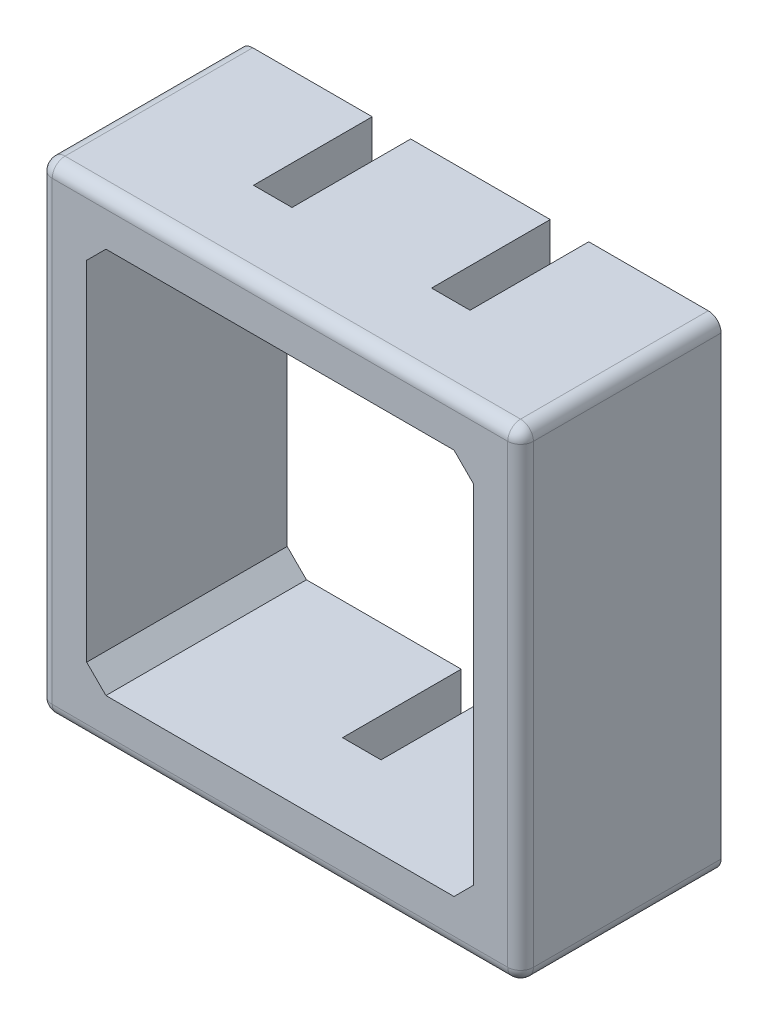
SolidWorks part; units mm, degrees
material "Nylon 101"
ref_plane "Front Plane" through (0, 0, 0) normal (0, 0, 1) x (1, 0, 0)
ref_plane "Top Plane" through (0, 0, 0) normal (0, 1, 0) x (1, 0, 0)
ref_plane "Right Plane" through (0, 0, 0) normal (1, 0, 0) x (0, 0, -1)
sketch "Sketch1" plane through (0, 0, 0) normal (0, 0, 1) x (1, 0, 0)
  line L0 (5.0482, -114.0142) -> (20.3517, -114.0142)
  line L1 (20.3517, -114.0142) -> (20.3517, -98.7107)
  line L2 (20.3517, -98.7107) -> (5.0482, -98.7107)
  line L3 (5.0482, -98.7107) -> (5.0482, -114.0142)
  line L4 (3.175, -115.8875) -> (22.225, -115.8875)
  line L5 (22.225, -115.8875) -> (22.225, -96.8375)
  line L6 (22.225, -96.8375) -> (3.175, -96.8375)
  line L7 (3.175, -96.8375) -> (3.175, -115.8875)
  line L8 (3.175, -115.8875) -> (22.225, -115.8875)
  line L9 (22.225, -115.8875) -> (22.225, -96.8375)
  line L10 (22.225, -96.8375) -> (3.175, -96.8375)
  line L11 (3.175, -96.8375) -> (3.175, -115.8875)
  dimension "D1" = 0
extrude "Boss-Extrude1" add sketch "Sketch1" against normal blind 7.9375
sketch "Sketch2" plane through (0, 0, -7.9375) normal (0, 0, -1) x (-1, 0, 0)
  line L0 (-12.065, -98.044) -> (-13.335, -98.044) construction
  line L1 (-9.8108, -98.044) -> (-8.5408, -98.044) construction
  line L2 (-16.8593, -98.044) -> (-15.5893, -98.044) construction
  line L3 (-12.7, -114.0142) -> (-12.7, -115.8875)
  line L4 (-5.0482, -114.0142) -> (-20.3517, -114.0142) construction
  line L5 (-3.175, -115.8875) -> (-22.225, -115.8875) construction
  line L6 (-9.1758, -98.7107) -> (-9.1758, -96.8375)
  line L7 (-20.3517, -98.7107) -> (-5.0482, -98.7107) construction
  line L8 (-22.225, -96.8375) -> (-3.175, -96.8375) construction
  line L9 (-16.2243, -98.7107) -> (-16.2243, -96.8375)
  point P0 (-12.7, -98.044)
  point P1 (-9.1758, -98.044)
  point P4 (-16.2243, -98.044)
extrude "Cut-Extrude-Thin1" cut sketch "Sketch2" against normal blind 4.699 thin contours L3 | L6 | L9 thin type mid plane wall 1.524
fillet "Fillet2" radius 0.508 8 edges at (3.175, -115.8875, -3.9688) (22.225, -115.8875, -3.9688) (3.175, -96.8375, -3.9688) (22.225, -96.8375, -3.9688) (22.225, -106.3625, 0) (12.7, -115.8875, 0) (3.175, -106.3625, 0) (12.7, -96.8375, 0)
chamfer "Chamfer1" distance 0.762 angle 45 4 edges at (20.3517, -98.7107, -3.9688) (5.0482, -98.7107, -3.9688) (5.0482, -114.0142, -3.9688) (20.3517, -114.0142, -3.9688)
hole_wizard "#0-80 Tapped Hole1" positions "Sketch4" profile "Sketch3" tap size "#0-80" standard "ANSI Inch"
sketch "Sketch4" plane through (0, 0, -7.9375) normal (0, 0, -1) x (-1, 0, 0)
  line L4 (-5.4292, -99.0917) -> (-3.3238, -96.9863) construction
  line L5 (-5.8102, -98.7107) -> (-5.0482, -99.4727) construction
  line L7 (-19.9707, -113.6332) -> (-22.0762, -115.7387) construction
  line L8 (-19.5897, -114.0142) -> (-20.3517, -113.2522) construction
  arc A2 (-3.175, -97.3455) -> (-3.683, -96.8375) centre (-3.683, -97.3455) ccw construction
  arc A3 (-22.225, -115.3795) -> (-21.717, -115.8875) centre (-21.717, -115.3795) ccw construction
  point P32 (-4.3765, -98.039)
  point P43 (-21.0235, -114.686)
cosmetic thread "Hole Thread1" parameters "D1"=2.794, "D2"=1.524
cosmetic thread "Hole Thread2" parameters "D1"=2.794, "D2"=1.524
sketch "Sketch3" plane through (4.3765, -98.039, -7.9375) normal (1, 0, 0) x (0, 1, 0)
  line L0 (0, 0) -> (0, 6.7079)
  line L1 (0, 6.7079) -> (0.5956, 6.35)
  line L2 (0.5956, 6.35) -> (0.5956, 0)
  line L5 (0.5956, 0) -> (0, 0)
  line L10 (0, 6.7079) -> (-0.5956, 6.35) construction
  line L11 (0, -6.35) -> (0, 107.95) construction
  dimension "Tap Drill Dia." = 1.1913
  dimension "Tap Drill Depth" = 6.35
  dimension "Drill Angle" = 118
